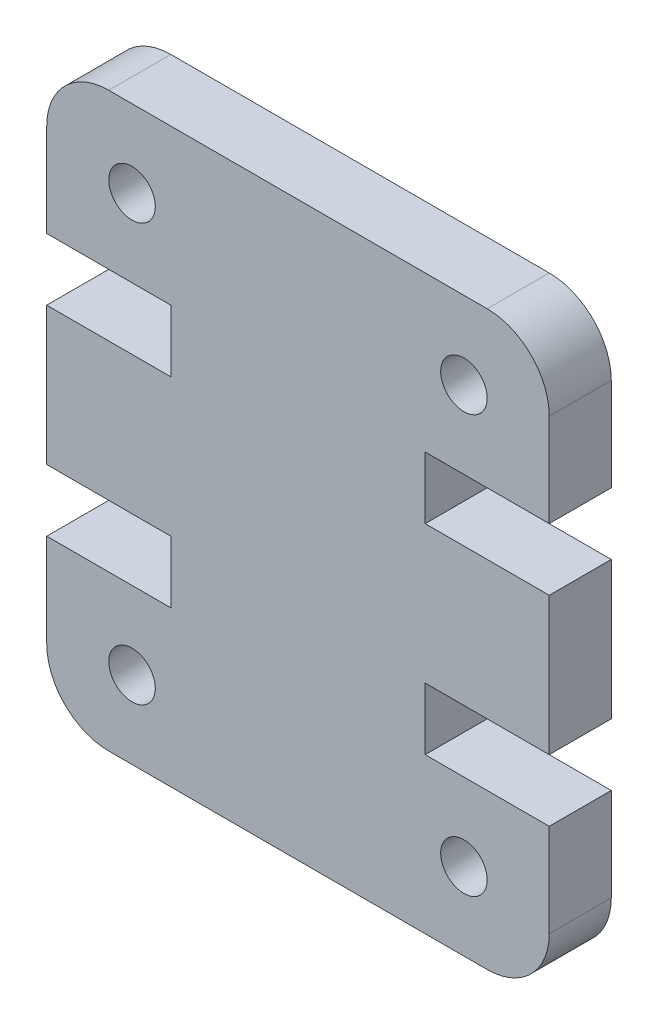
SolidWorks part; units mm, degrees
ref_plane "Front Plane" through (0, 0, 0) normal (0, 0, 1) x (1, 0, 0)
ref_plane "Top Plane" through (0, 0, 0) normal (0, 1, 0) x (1, 0, 0)
ref_plane "Right Plane" through (0, 0, 0) normal (1, 0, 0) x (0, 0, -1)
sketch "Sketch2" plane through (0, 0, 0) normal (0, 0, 1) x (1, 0, 0)
  line L0 (2, 18.45) -> (14.2, 18.45)
  line L1 (2, 0) -> (14.2, 0)
  line L2 (4, 13.45) -> (4, 11.45)
  line L3 (16.2, 13.45) -> (12.2, 13.45)
  line L4 (0, 13.45) -> (4, 13.45)
  line L5 (4, 11.45) -> (0, 11.45)
  line L6 (12.2, 13.45) -> (12.2, 11.45)
  line L7 (12.2, 11.45) -> (16.2, 11.45)
  line L8 (4, 7) -> (4, 5)
  line L9 (12.2, 7) -> (12.2, 5)
  line L10 (0, 7) -> (4, 7)
  line L11 (4, 5) -> (0, 5)
  line L12 (12.2, 5) -> (16.2, 5)
  line L13 (16.2, 7) -> (12.2, 7)
  line L14 (16.2, 16.45) -> (16.2, 13.45)
  line L15 (16.2, 5) -> (16.2, 2)
  line L16 (16.2, 11.45) -> (16.2, 7)
  line L17 (0, 16.45) -> (0, 13.45)
  line L18 (0, 11.45) -> (0, 7)
  line L19 (0, 5) -> (0, 2)
  arc A0 (2, 18.45) -> (0, 16.45) centre (2, 16.45) ccw
  arc A1 (16.2, 16.45) -> (14.2, 18.45) centre (14.2, 16.45) ccw
  arc A2 (14.2, 0) -> (16.2, 2) centre (14.2, 2) ccw
  arc A3 (0, 2) -> (2, 0) centre (2, 2) ccw
  circle A4 centre (13.45, 2.5) radius 0.75
  circle A5 centre (2.75, 2.5) radius 0.75
  circle A6 centre (13.45, 15.95) radius 0.75
  circle A7 centre (2.75, 15.95) radius 0.75
extrude "Boss-Extrude1" add sketch "Sketch2" along normal blind 2
